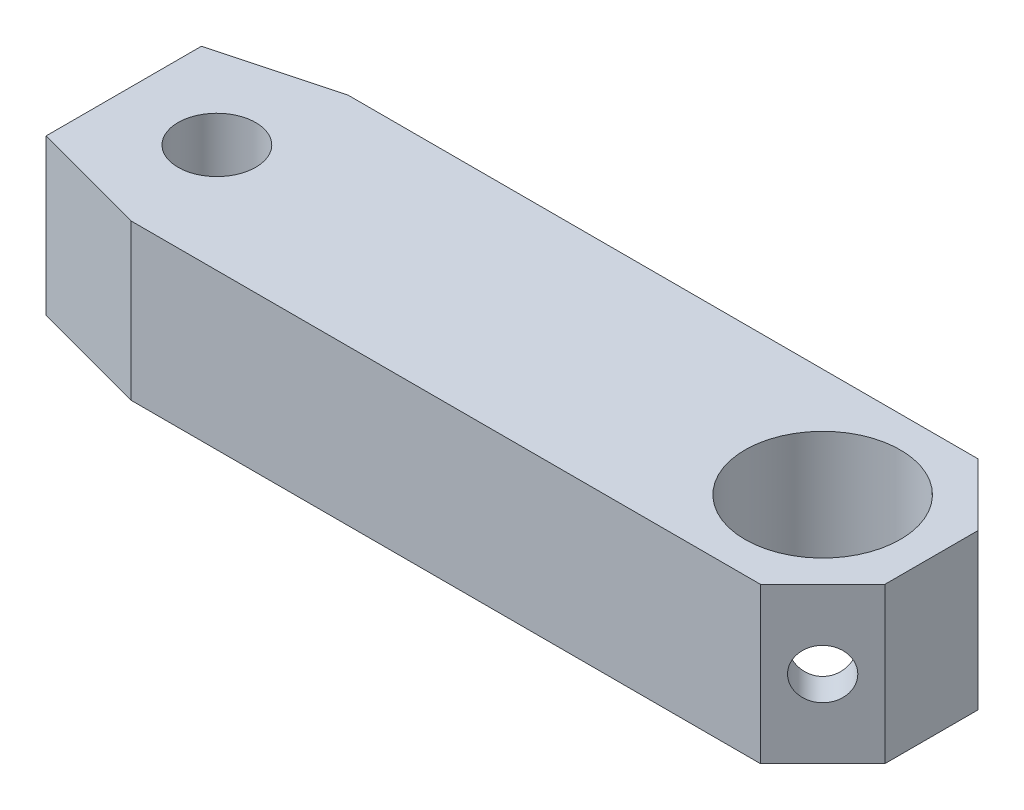
SolidWorks part; units mm, degrees
ref_plane "Front Plane" through (0, 0, 0) normal (0, 0, 1) x (1, 0, 0)
ref_plane "Top Plane" through (0, 0, 0) normal (0, 1, 0) x (1, 0, 0)
ref_plane "Right Plane" through (0, 0, 0) normal (1, 0, 0) x (0, 0, -1)
sketch "block" plane through (0, 0, 0) normal (0, 1, 0) x (1, 0, 0)
  line L0 (19.5, 0) -> (23, 3.5) construction
  line L1 (0.7321, 3.5) -> (21, 3.5)
  line L2 (-3, 2.5) -> (-3, -2.5)
  line L3 (0.7321, -3.5) -> (21, -3.5)
  line L4 (23, 1.5) -> (23, -1.5)
  line L5 (-3, 3.5) -> (23, -3.5) construction
  line L6 (-3, -3.5) -> (23, 3.5) construction
  line L7 (21, 3.5) -> (23, 1.5)
  line L8 (-3, -2.5) -> (0.7321, -3.5)
  line L9 (0.7321, 3.5) -> (-3, 2.5)
  line L10 (21, -3.5) -> (23, -1.5)
  circle A0 centre (19.5, 0) radius 2.5
  point P0 (0, 0)
  point P4 (10, 0)
  point P11 (22, 2.5)
  point P21 (22, -2.5)
  dimension "D2" = 5
  dimension "D1" = 19.5
  dimension "D3" = 0
  dimension "D4" = 0
  dimension "D5" = 3
  dimension "D6" = 3.5
  dimension "D7" = 3.5
  dimension "D8" = 29.932
  dimension "D9" = 2
  dimension "D10" = 45
  dimension "D11" = 1
  dimension "D12" = 75
  dimension "D13" = 1
  dimension "D14" = 75
  dimension "D15" = 2
  dimension "D16" = 45
extrude "Boss-Extrude1" add sketch "block" against normal blind 5 contours L1 L9 L2 L8 L3 L4 L7 A0 region at (8.7584, 0, 0)
hole_wizard "M3 Tapped Hole1" positions "Sketch4" profile "Sketch5" tap size "M3" standard "ISO" end condition through all
sketch "Sketch4" plane through (0, 0, 0) normal (0, 1, 0) x (1, 0, 0)
  line L0 (0, -2.75) -> (0, 2.75) construction
  line L1 (-2.75, 0) -> (2.75, 0) construction
  point P0 (0, 0)
  dimension "D1" = 0
  dimension "D2" = 0
sketch "Sketch5" plane through (0, 0, 0) normal (1, 0, 0) x (0, 0, 1)
  line L0 (0, 0) -> (0, 5)
  line L1 (0, 5) -> (1.25, 5)
  line L2 (1.25, 5) -> (1.25, 0)
  line L5 (1.25, 0) -> (0, 0)
  line L11 (0, -6.35) -> (0, 107.95) construction
  dimension "Thru Tap Drill Dia." = 2.5
  dimension "Thru Tap Drill Depth" = 5
cosmetic thread "Hole Thread1" parameters "D2"=3
hole_wizard "M2 Tapped Hole1" positions "Sketch8" profile "Sketch9" tap size "M2" standard "ISO" end condition up to next
sketch "Sketch8" plane through (12.25, 0, -12.25) normal (0.7071, 0, -0.7071) x (-0.7071, 0, -0.7071)
  line L0 (-13.7886, 0) -> (-13.7886, -5) construction
  line L1 (-12.3744, 0) -> (-15.2028, 0) construction
  line L2 (-12.3744, -5) -> (-15.2028, -5) construction
  line L3 (-13.7886, -5) -> (-13.7886, -2.5) construction
  line L4 (-13.7886, -2.5) -> (-15.2028, -2.5) construction
  line L5 (-15.2028, -5) -> (-15.2028, 0) construction
  point P0 (-13.7886, -2.5)
  dimension "D1" = 0
  dimension "D2" = 0
sketch "Sketch9" plane through (22, -2.5, -2.5) normal (0, 1, 0) x (-0.7071, 0, -0.7071)
  line L0 (0, 0) -> (0, 1.0355)
  line L1 (0, 1.0355) -> (0.8, 1.0355)
  line L2 (0.8, 1.0355) -> (0.8, 0)
  line L5 (0.8, 0) -> (0, 0)
  line L11 (0, -6.35) -> (0, 107.95) construction
  dimension "Thru Tap Drill Dia." = 1.6
  dimension "Thru Tap Drill Depth" = 1.0355
cosmetic thread "Hole Thread3" parameters "D2"=2
mirror "Mirror1" about plane through (0, 0, 0) normal (0, 0, 1) of "M2 Tapped Hole1"
cosmetic thread "Hole Thread4" parameters "D2"=2
equation "\"D6@block\" = \"D2@block\" / 2 + 1"
equation "\"D7@block\" = \"D2@block\" / 2 + 1"
equation "\"D1@block\"=\"D2@block\"/2+17mm"
